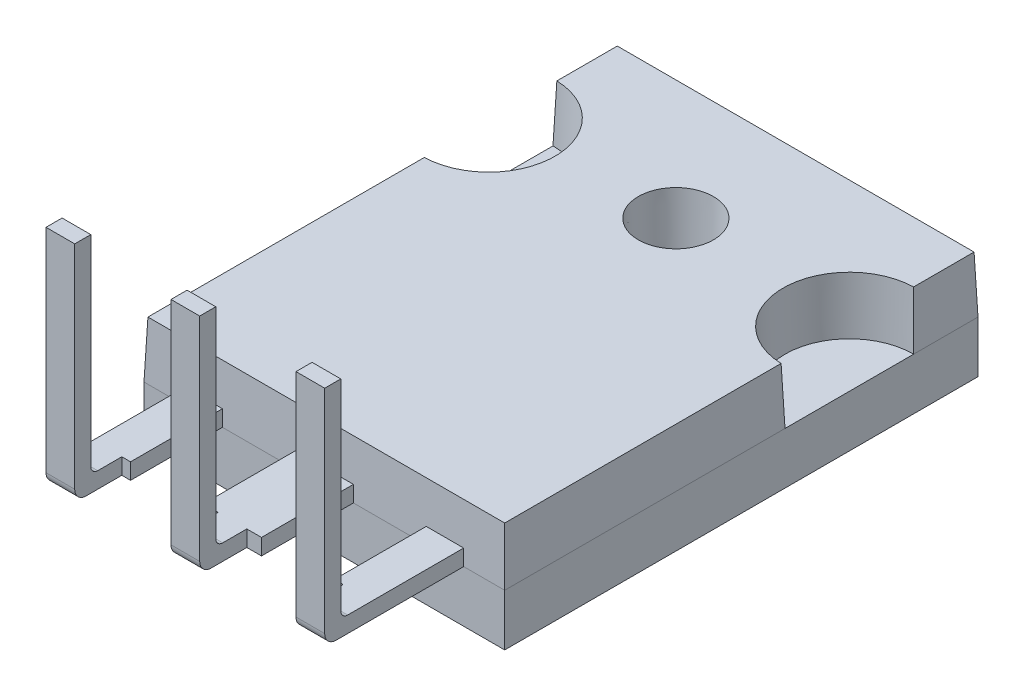
SolidWorks part; units mm, degrees
ref_plane "Front" through (0, 0, 0) normal (0, 0, 1) x (1, 0, 0)
ref_plane "Top" through (0, 0, 0) normal (0, 1, 0) x (1, 0, 0)
ref_plane "Right" through (0, 0, 0) normal (1, 0, 0) x (0, 0, -1)
sketch "Эскиз1" plane through (0, 0, 0) normal (0, 1, 0) x (1, 0, 0)
  line L0 (0, 5) -> (0, 10.3) construction
  line L1 (7.85, -10.3) -> (-7.85, -10.3)
  line L2 (7.85, -10.3) -> (7.85, 10.3)
  line L3 (7.85, 10.3) -> (-7.85, 10.3)
  line L4 (-7.85, -10.3) -> (-7.85, 10.3)
  line L5 (7.85, -10.3) -> (-7.85, 10.3) construction
  line L6 (7.85, 10.3) -> (-7.85, -10.3) construction
  circle A0 centre (0, 5) radius 1.55
  point P0 (0, 0)
  dimension "D3" = 3.1
  dimension "D1" = 20.6
  dimension "D2" = 15.7
  dimension "D4" = 5.3
extrude "Бобышка-Вытянуть1" add sketch "Эскиз1" along normal blind 2.25
sketch "Эскиз2" plane through (0, 2.25, 0) normal (0, 1, 0) x (1, 0, 0)
  line L0 (-7.85, 1.9) -> (-7.85, -10.3)
  line L1 (7.85, 7.5) -> (7.85, 10.3)
  line L2 (0, -0.5774) -> (0, -50000.5774) construction
  line L3 (-6.065, -10.3) -> (-4.435, -10.3)
  line L4 (-7.85, 10.3) -> (-7.85, -10.3)
  line L5 (-7.85, -10.3) -> (7.85, -10.3)
  line L6 (7.85, -10.3) -> (7.85, 10.3)
  line L7 (7.85, 10.3) -> (-7.85, 10.3)
  line L8 (-7.85, 10.3) -> (-7.85, 7.5)
  line L9 (-7.85, -10.3) -> (7.85, -10.3)
  line L10 (7.85, -10.3) -> (7.85, 1.9)
  line L11 (7.85, 10.3) -> (-7.85, 10.3)
  line L12 (-6.065, -10.3) -> (-6.065, -14.3)
  line L13 (-6.065, -14.3) -> (-4.435, -14.3)
  line L14 (-4.435, -10.3) -> (-4.435, -14.3)
  line L15 (-6.065, -10.3) -> (-4.435, -14.3) construction
  line L16 (-6.065, -14.3) -> (-4.435, -10.3) construction
  line L17 (-1.265, -10.3) -> (1.265, -10.3)
  line L18 (-1.265, -10.3) -> (-1.265, -14.3)
  line L19 (-1.265, -14.3) -> (1.265, -14.3)
  line L20 (1.265, -10.3) -> (1.265, -14.3)
  line L21 (-1.265, -10.3) -> (1.265, -14.3) construction
  line L22 (-1.265, -14.3) -> (1.265, -10.3) construction
  line L23 (4.435, -10.3) -> (6.065, -10.3)
  line L24 (4.435, -10.3) -> (4.435, -14.3)
  line L25 (4.435, -14.3) -> (6.065, -14.3)
  line L26 (6.065, -10.3) -> (6.065, -14.3)
  line L27 (4.435, -10.3) -> (6.065, -14.3) construction
  line L28 (4.435, -14.3) -> (6.065, -10.3) construction
  line L29 (-5.25, -0.5774) -> (-5.25, -50000.5774) construction
  line L30 (5.25, -0.5774) -> (5.25, -50000.5774) construction
  line L32 (-0.625, -14.3) -> (0.625, -14.3)
  line L33 (-0.625, -14.3) -> (-0.625, -16.35)
  line L34 (-0.625, -16.35) -> (0.625, -16.35)
  line L35 (0.625, -14.3) -> (0.625, -16.35)
  line L36 (-0.625, -14.3) -> (0.625, -16.35) construction
  line L37 (-0.625, -16.35) -> (0.625, -14.3) construction
  line L38 (-6.065, -14.3) -> (-4.815, -14.3)
  line L39 (-6.065, -14.3) -> (-6.065, -16.35)
  line L40 (-6.065, -16.35) -> (-4.815, -16.35)
  line L41 (-4.815, -14.3) -> (-4.815, -16.35)
  line L42 (-6.065, -14.3) -> (-4.815, -16.35) construction
  line L43 (-6.065, -16.35) -> (-4.815, -14.3) construction
  line L44 (6.065, -14.3) -> (4.815, -14.3)
  line L45 (6.065, -14.3) -> (6.065, -16.35)
  line L46 (6.065, -16.35) -> (4.815, -16.35)
  line L47 (4.815, -14.3) -> (4.815, -16.35)
  line L48 (6.065, -14.3) -> (4.815, -16.35) construction
  line L49 (6.065, -16.35) -> (4.815, -14.3) construction
  circle A0 centre (0, 5) radius 1.55 construction
  circle A1 centre (0, 5) radius 1.55
  arc A2 (-7.85, 1.9) -> (-7.85, 7.5) centre (-7.85, 4.7) ccw
  arc A3 (7.85, 7.5) -> (7.85, 1.9) centre (7.85, 4.7) ccw
  point P17 (-5.25, -12.3)
  point P22 (0, -12.3)
  point P27 (5.25, -12.3)
  point P42 (0, -15.325)
  point P43 (-5.44, -15.325)
  point P47 (5.44, -15.325)
  point P48 (0, 0)
  line M15 (-7.85, 10.3) -> (-7.85, -10.3)
  line M16 (-7.85, -10.3) -> (7.85, -10.3)
  line M17 (7.85, -10.3) -> (7.85, 10.3)
  line M18 (7.85, 10.3) -> (-7.85, 10.3)
  circle M19 centre (0, 5) radius 1.55
  dimension "D4" = 5.6
  dimension "D2" = 5.6
  dimension "D3" = 5.6
  dimension "D7" = 1.63
  dimension "D8" = 2.53
  dimension "D9" = 4
  dimension "D10" = 1.25
  dimension "D11" = 21.35
  dimension "D1" = 0
  dimension "D5" = 5.25
  dimension "D6" = 5.25
extrude "Бобышка-Вытянуть2" add sketch "Эскиз2" along normal blind 2.45 draft 2 contours A3 A2 L9 M17 M18 M15 M16 M19 region at (0, 2.25, 0.5271)
extrude "Бобышка-Вытянуть3" add sketch "Эскиз2<4>" along normal blind 0.7 separate body contours L14 L12 L13 M16 | L41 L13 L39 L40 | L20 L9 L18 L19 | L35 L19 L33 L34 | L26 L9 L24 L25 | L25 L47 L46 L45 region at (-5.25, 2.25, 12.3) region at (-5.44, 2.25, 15.325) region at (0, 2.25, 12.3) region at (5.25, 2.25, 12.3) region at (0, 2.25, 15.325) region at (5.44, 2.25, 15.325)
sketch "Эскиз2<4>" plane through (0, 2.25, 0) normal (0, 1, 0) x (1, 0, 0) same geometry as "Эскиз2"
sketch "Эскиз3" plane through (0, 2.95, 0) normal (0, 1, 0) x (1, 0, 0)
  line L0 (-4.815, -14.3) -> (-4.815, -16.35) construction
  line L1 (-6.065, -16.35) -> (-4.815, -16.35)
  line L2 (-6.065, -16.35) -> (-6.065, -15.65)
  line L3 (-6.065, -15.65) -> (-4.815, -15.65)
  line L4 (-4.815, -16.35) -> (-4.815, -15.65)
  line L5 (-6.065, -16.35) -> (-4.815, -15.65) construction
  line L6 (-6.065, -15.65) -> (-4.815, -16.35) construction
  line L7 (0.625, -14.3) -> (0.625, -16.35) construction
  line L8 (-0.625, -16.35) -> (0.625, -16.35)
  line L9 (-0.625, -16.35) -> (-0.625, -15.65)
  line L10 (-0.625, -15.65) -> (0.625, -15.65)
  line L11 (0.625, -16.35) -> (0.625, -15.65)
  line L12 (-0.625, -16.35) -> (0.625, -15.65) construction
  line L13 (-0.625, -15.65) -> (0.625, -16.35) construction
  line L14 (6.065, -10.3) -> (6.065, -16.35) construction
  line L15 (4.815, -16.35) -> (6.065, -16.35)
  line L16 (4.815, -16.35) -> (4.815, -15.65)
  line L17 (4.815, -15.65) -> (6.065, -15.65)
  line L18 (6.065, -16.35) -> (6.065, -15.65)
  line L19 (4.815, -16.35) -> (6.065, -15.65) construction
  line L20 (4.815, -15.65) -> (6.065, -16.35) construction
  point P4 (-5.44, -16)
  point P12 (0, -16)
  point P20 (5.44, -16)
  dimension "D1" = 0.7
extrude "Бобышка-Вытянуть4" add sketch "Эскиз3" along normal blind 9.05
fillet "Скругление1" radius 0.3 1 edges at (5.44, 2.95, 15.65)
fillet "Скругление2" radius 0.3 1 edges at (0, 2.95, 15.65)
fillet "Скругление3" radius 0.3 1 edges at (-5.44, 2.95, 15.65)
fillet "Скругление4" radius 0.5 1 edges at (5.44, 2.25, 16.35)
fillet "Скругление5" radius 0.5 1 edges at (0, 2.25, 16.35)
fillet "Скругление6" radius 0.5 1 edges at (-5.44, 2.25, 16.35)
